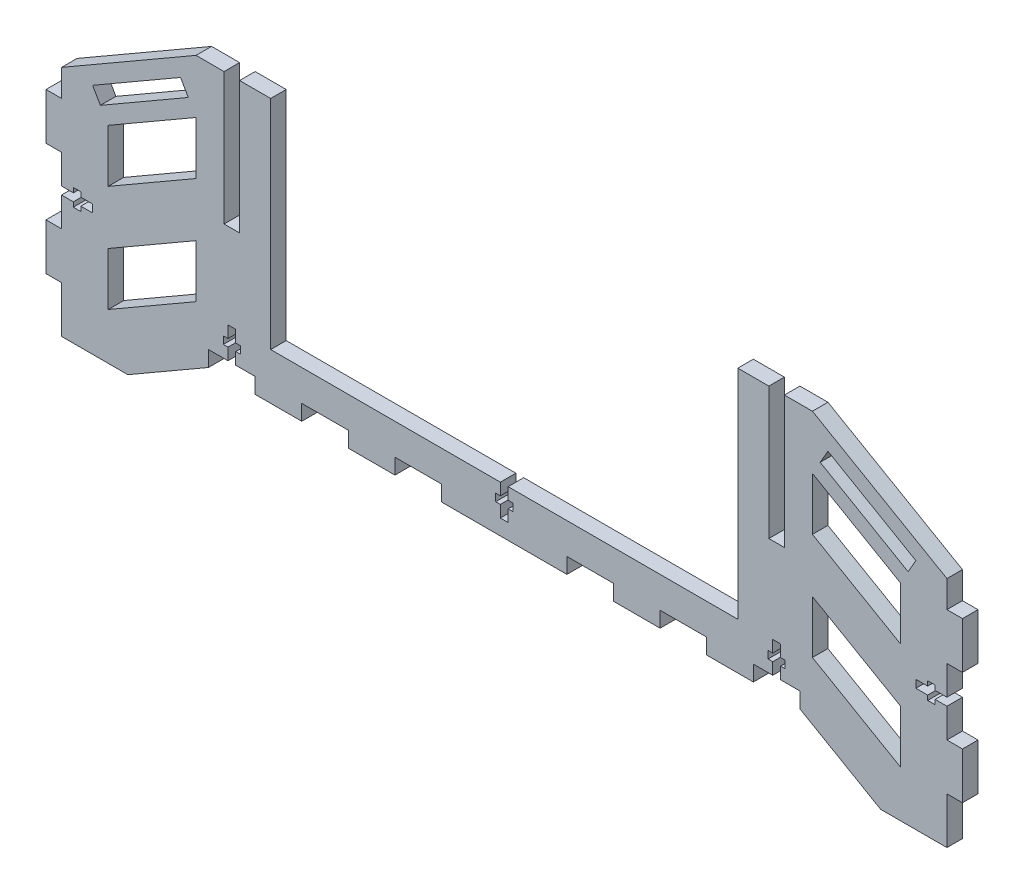
SolidWorks part; units mm, degrees
material "PMMA"
ref_plane "Front Plane" through (0, 0, 0) normal (0, 0, 1) x (1, 0, 0)
ref_plane "Top Plane" through (0, 0, 0) normal (0, 1, 0) x (1, 0, 0)
ref_plane "Right Plane" through (0, 0, 0) normal (1, 0, 0) x (0, 0, -1)
sketch "Schizzo1" plane through (0, 0, 0) normal (0, 0, 1) x (1, 0, 0)
  line L0 (-142.5, 75) -> (-142.5, 66.3397)
  line L1 (-142.5, 0) -> (142.5, 0)
  line L2 (142.5, 75) -> (142.5, 66.3397)
  line L3 (142.5, 75) -> (99.1987, 100)
  line L4 (99.1987, 100) -> (-99.1987, 100)
  line L5 (-99.1987, 100) -> (-142.5, 75)
  line L6 (95.1795, 85) -> (-95.1795, 85) construction
  line L7 (-95.1795, 85) -> (-127.5, 66.3397) construction
  line L8 (-127.5, 66.3397) -> (-127.5, 15) construction
  line L9 (-127.5, 15) -> (127.5, 15) construction
  line L10 (127.5, 15) -> (127.5, 66.3397) construction
  line L11 (127.5, 66.3397) -> (95.1795, 85) construction
  line L12 (-95.1795, 85) -> (-95.1795, 15) construction
  line L13 (95.1795, 85) -> (95.1795, 15) construction
  line L14 (-127.5, 66.3397) -> (127.5, 66.3397) construction
  line L15 (-142.5, 66.3397) -> (-147.5, 66.3397)
  line L16 (-147.5, 66.3397) -> (-147.5, 51.3397)
  line L17 (-147.5, 51.3397) -> (-142.5, 51.3397)
  line L18 (-142.5, 51.3397) -> (-142.5, 30)
  line L19 (-142.5, 30) -> (-147.5, 30)
  line L20 (-147.5, 30) -> (-147.5, 15)
  line L21 (-147.5, 15) -> (-142.5, 15)
  line L22 (-142.5, 15) -> (-142.5, 0)
  line L23 (-142.5, 75) -> (-142.5, 0) construction
  line L24 (142.5, 66.3397) -> (147.5, 66.3397)
  line L25 (142.5, 0) -> (142.5, 75) construction
  line L26 (147.5, 66.3397) -> (147.5, 51.3397)
  line L27 (147.5, 51.3397) -> (142.5, 51.3397)
  line L28 (142.5, 51.3397) -> (142.5, 30)
  line L29 (142.5, 30) -> (147.5, 30)
  line L30 (147.5, 30) -> (147.5, 15)
  line L31 (147.5, 15) -> (142.5, 15)
  line L32 (142.5, 15) -> (142.5, 0)
  point P2 (0, 0)
  dimension "D1" = 5
  dimension "D2" = 285
  dimension "D3" = 100
  dimension "D4" = 75
  dimension "D5" = 198.3975
  dimension "D7" = 190.359
  dimension "D8" = 15
  dimension "D9" = 150
  dimension "D10" = 21.3397
  dimension "D6" = 15
extrude "Estrusione-Estrusione1" add sketch "Schizzo1" along normal blind 5
sketch "Schizzo2" plane through (0, 0, 0) normal (0, 0, 1) x (1, 0, 0)
  line L0 (-99.1987, 82.6795) -> (-127.5, 66.3397)
  line L1 (-113.3494, 74.5096) -> (-120.8494, 87.5) construction
  line L2 (0, 0) -> (0, 100) construction
  line L3 (99.1987, 100) -> (-99.1987, 100) construction
  line L4 (-127.5, 49.3301) -> (-127.5, 66.3397)
  line L5 (99.1987, 31.3397) -> (99.1987, 48.3494)
  line L6 (-99.1987, 100) -> (-99.1987, 0) construction
  line L7 (99.1987, 31.3397) -> (127.5, 15)
  line L8 (127.5, 32.0096) -> (127.5, 15)
  line L9 (-95.1795, 15) -> (-121.1603, 0)
  line L10 (99.1987, 48.3494) -> (127.5, 32.0096)
  line L11 (-121.1603, 0) -> (121.1603, 0)
  line L12 (121.1603, 0) -> (95.1795, 15)
  line L13 (95.1795, 15) -> (-95.1795, 15)
  line L14 (-142.5, 0) -> (142.5, 0) construction
  line L15 (-99.1987, 31.3397) -> (-127.5, 15)
  line L16 (-99.1987, 65.6699) -> (-99.1987, 82.6795)
  line L17 (99.1987, 65.6699) -> (99.1987, 82.6795)
  line L18 (127.5, 49.3301) -> (99.1987, 65.6699)
  line L19 (127.5, 49.3301) -> (127.5, 66.3397)
  line L20 (-127.5, 49.3301) -> (-99.1987, 65.6699)
  line L21 (-99.1987, 48.3494) -> (-127.5, 32.0096)
  line L22 (-127.5, 32.0096) -> (-127.5, 15)
  line L23 (-99.1987, 31.3397) -> (-99.1987, 48.3494)
  line L24 (99.1987, 82.6795) -> (127.5, 66.3397)
  line L25 (-99.1987, 100) -> (-142.5, 75) construction
  line L26 (-127.5, 66.3397) -> (-135, 79.3301) construction
  line L27 (-132.5, 75) -> (-104.1987, 91.3397)
  line L28 (-132.5, 75) -> (-130, 70.6699)
  line L29 (-130, 70.6699) -> (-101.6987, 87.0096)
  line L30 (-104.1987, 91.3397) -> (-101.6987, 87.0096)
  line L31 (132.5, 75) -> (130, 70.6699)
  line L32 (132.5, 75) -> (104.1987, 91.3397)
  line L33 (104.1987, 91.3397) -> (101.6987, 87.0096)
  line L34 (130, 70.6699) -> (101.6987, 87.0096)
  point P42 (-131.25, 72.8349)
  point P44 (-131.25, 72.8349)
  point P46 (-115.8494, 78.8397)
  point P47 (-118.3494, 83.1699)
  dimension "D1" = 15
  dimension "D3" = 5
extrude "Taglio-Estrusione2" cut sketch "Schizzo2" along direction (0, 0, 1) on the side of the normal through all
sketch "Schizzo5" plane through (0, 0, 0) normal (0, 0, 1) x (1, 0, 0)
  line L0 (-95.1795, 15) -> (-95.1795, 20)
  line L1 (-95.1795, 20) -> (-80.1795, 20)
  line L2 (-80.1795, 20) -> (-80.1795, 15)
  line L3 (-80.1795, 15) -> (-95.1795, 15)
  line L4 (-65.1795, 20) -> (-65.1795, 15)
  line L5 (-65.1795, 15) -> (-50.1795, 15)
  line L6 (-50.1795, 15) -> (-50.1795, 20)
  line L7 (-50.1795, 20) -> (-65.1795, 20)
  line L8 (-35.1795, 15) -> (-35.1795, 20)
  line L9 (-35.1795, 20) -> (-20.1795, 20)
  line L10 (-20.1795, 20) -> (-20.1795, 15)
  line L11 (-20.1795, 15) -> (-35.1795, 15)
  line L12 (-127.5, 15) -> (127.5, 15) construction
  line L13 (-95.1795, 85) -> (-95.1795, 15) construction
  line L14 (0, 15) -> (0, 100) construction
  line L15 (35.1795, 15) -> (35.1795, 20)
  line L16 (20.1795, 15) -> (35.1795, 15)
  line L17 (20.1795, 20) -> (20.1795, 15)
  line L18 (35.1795, 20) -> (20.1795, 20)
  line L19 (50.1795, 15) -> (50.1795, 20)
  line L20 (65.1795, 15) -> (50.1795, 15)
  line L21 (65.1795, 20) -> (65.1795, 15)
  line L22 (50.1795, 20) -> (65.1795, 20)
  line L23 (95.1795, 15) -> (95.1795, 20)
  line L24 (80.1795, 15) -> (95.1795, 15)
  line L25 (80.1795, 20) -> (80.1795, 15)
  line L26 (95.1795, 20) -> (80.1795, 20)
  line L27 (-95.1795, 57.5) -> (95.1795, 57.5) construction
  line L28 (-95.1795, 15) -> (-121.1603, 0) construction
  line L29 (95.1795, 85) -> (95.1795, 15) construction
  line L30 (99.1987, 100) -> (-99.1987, 100) construction
  line L31 (90.1795, 100) -> (85.1795, 100)
  line L32 (-90.1795, 100) -> (-85.1795, 100)
  line L33 (-90.1795, 100) -> (-90.1795, 57.5)
  line L34 (-90.1795, 57.5) -> (-85.1795, 57.5)
  line L35 (-85.1795, 100) -> (-85.1795, 57.5)
  line L36 (90.1795, 100) -> (90.1795, 57.5)
  line L37 (90.1795, 57.5) -> (85.1795, 57.5)
  line L38 (85.1795, 100) -> (85.1795, 57.5)
  line L40 (-75.1795, 100) -> (75.1795, 100)
  line L41 (-75.1795, 100) -> (-75.1795, 30)
  line L42 (-75.1795, 30) -> (75.1795, 30)
  line L43 (75.1795, 100) -> (75.1795, 30)
  dimension "D1" = 5
  dimension "D2" = 15
  dimension "D3" = 15
  dimension "D4" = 15
  dimension "D5" = 42.5
  dimension "D6" = 42.5
  dimension "D7" = 5
  dimension "D8" = 5
  dimension "D9" = 10
  dimension "D10" = 10
  dimension "D11" = 15
  dimension "D12" = 190.359
  dimension "D13" = 40.359
extrude "Taglio-Estrusione3" cut sketch "Schizzo5" along direction (0, 0, 1) on the side of the normal through all
sketch "Schizzo6" plane through (0, 0, 0) normal (0, 0, 1) x (1, 0, 0)
  line L0 (-142.5, 51.3397) -> (-142.5, 30) construction
  line L1 (-142.5, 40.6699) -> (-120, 40.6699) construction
  line L2 (-142.5, 41.9199) -> (-138.7, 41.9199)
  line L3 (-138.7, 41.9199) -> (-138.7, 43.4199)
  line L4 (-138.7, 43.4199) -> (-136.3, 43.4199)
  line L5 (-136.3, 43.4199) -> (-136.3, 41.9199)
  line L6 (-136.3, 41.9199) -> (-132.5, 41.9199)
  line L7 (-132.5, 41.9199) -> (-132.5, 39.4199)
  line L8 (-132.5, 39.4199) -> (-136.3, 39.4199)
  line L9 (-136.3, 39.4199) -> (-136.3, 37.9199)
  line L10 (-136.3, 37.9199) -> (-138.7, 37.9199)
  line L11 (-138.7, 37.9199) -> (-138.7, 39.4199)
  line L12 (-138.7, 39.4199) -> (-142.5, 39.4199)
  line L13 (-142.5, 39.4199) -> (-142.5, 41.9199)
  line L14 (0, 0) -> (0, 100) construction
  line L15 (136.3, 43.4199) -> (136.3, 41.9199)
  line L16 (138.7, 43.4199) -> (136.3, 43.4199)
  line L17 (138.7, 41.9199) -> (138.7, 43.4199)
  line L18 (142.5, 41.9199) -> (138.7, 41.9199)
  line L19 (142.5, 39.4199) -> (142.5, 41.9199)
  line L20 (138.7, 39.4199) -> (142.5, 39.4199)
  line L21 (138.7, 37.9199) -> (138.7, 39.4199)
  line L22 (136.3, 37.9199) -> (138.7, 37.9199)
  line L23 (136.3, 39.4199) -> (136.3, 37.9199)
  line L24 (132.5, 39.4199) -> (136.3, 39.4199)
  line L25 (132.5, 41.9199) -> (132.5, 39.4199)
  line L26 (136.3, 41.9199) -> (132.5, 41.9199)
  line L27 (-90.1795, 57.5) -> (-85.1795, 57.5) construction
  line L28 (-87.6795, 57.5) -> (-87.6795, 2.5) construction
  line L29 (-80.1795, 20) -> (-95.1795, 20) construction
  line L30 (85.1795, 57.5) -> (90.1795, 57.5) construction
  line L31 (87.6795, 57.5) -> (87.6795, 20) construction
  line L32 (95.1795, 20) -> (80.1795, 20) construction
  line L33 (-87.6795, 20) -> (-87.6795, 30) construction
  line L34 (-88.9295, 20) -> (-88.9295, 23.8)
  line L35 (-88.9295, 23.8) -> (-90.4295, 23.8)
  line L36 (-90.4295, 23.8) -> (-90.4295, 26.2)
  line L37 (-90.4295, 26.2) -> (-88.9295, 26.2)
  line L38 (-88.9295, 26.2) -> (-88.9295, 30)
  line L39 (-88.9295, 30) -> (-86.4295, 30)
  line L40 (-86.4295, 30) -> (-86.4295, 26.2)
  line L41 (-86.4295, 26.2) -> (-84.9295, 26.2)
  line L42 (-84.9295, 26.2) -> (-84.9295, 23.8)
  line L43 (-84.9295, 23.8) -> (-86.4295, 23.8)
  line L44 (-86.4295, 23.8) -> (-86.4295, 20)
  line L45 (-86.4295, 20) -> (-88.9295, 20)
  line L46 (86.4295, 20) -> (88.9295, 20)
  line L47 (86.4295, 23.8) -> (86.4295, 20)
  line L48 (84.9295, 23.8) -> (86.4295, 23.8)
  line L49 (84.9295, 26.2) -> (84.9295, 23.8)
  line L50 (86.4295, 26.2) -> (84.9295, 26.2)
  line L51 (86.4295, 30) -> (86.4295, 26.2)
  line L52 (88.9295, 30) -> (86.4295, 30)
  line L53 (88.9295, 26.2) -> (88.9295, 30)
  line L54 (90.4295, 26.2) -> (88.9295, 26.2)
  line L55 (90.4295, 23.8) -> (90.4295, 26.2)
  line L56 (88.9295, 23.8) -> (90.4295, 23.8)
  line L57 (88.9295, 20) -> (88.9295, 23.8)
  line L58 (0, 32.4779) -> (0, 27.5221) construction
  line L59 (0, 20) -> (0, 30) construction
  line L60 (-1.25, 20) -> (-1.25, 23.8)
  line L61 (-1.25, 23.8) -> (-2.75, 23.8)
  line L62 (-2.75, 23.8) -> (-2.75, 26.2)
  line L63 (-2.75, 26.2) -> (-1.25, 26.2)
  line L64 (-1.25, 26.2) -> (-1.25, 30)
  line L65 (-1.25, 30) -> (1.25, 30)
  line L66 (1.25, 30) -> (1.25, 26.2)
  line L67 (1.25, 26.2) -> (2.75, 26.2)
  line L68 (2.75, 26.2) -> (2.75, 23.8)
  line L69 (2.75, 23.8) -> (1.25, 23.8)
  line L70 (1.25, 23.8) -> (1.25, 20)
  line L71 (1.25, 20) -> (-1.25, 20)
  line L73 (-75.1795, 30) -> (75.1795, 30) construction
  dimension "D1" = 5.5
  dimension "D2" = 2.5
  dimension "D3" = 1.25
  dimension "D4" = 2.75
  dimension "D5" = 2.4
  dimension "D6" = 10
  dimension "D7" = 5.5
  dimension "D8" = 2.5
  dimension "D9" = 1.25
  dimension "D10" = 2.75
  dimension "D11" = 2.4
  dimension "D12" = 10
  dimension "D13" = 90
  dimension "D14" = 90
  dimension "D15" = 5.5
  dimension "D16" = 2.5
  dimension "D17" = 1.25
  dimension "D18" = 2.75
  dimension "D19" = 2.4
  dimension "D20" = 10
  dimension "D21" = 90
  dimension "D22" = 90
extrude "Taglio-Estrusione4" cut sketch "Schizzo6" along direction (0, 0, 1) on the side of the normal through all
equation "\"Thickness\"=5"
equation "\"D1@Estrusione-Estrusione1\"=\"Thickness\""
equation "\"D1@Schizzo5\"=\"Thickness\""
equation "\"D7@Schizzo5\"=\"Thickness\""
equation "\"D9@Schizzo5\"=2*\"Thickness\""
equation "\"D10@Schizzo5\"=2*\"Thickness\""
equation "\"D1@Schizzo1\"=\"Thickness\""
equation "\"D3@Schizzo2\"=\"Thickness\""
